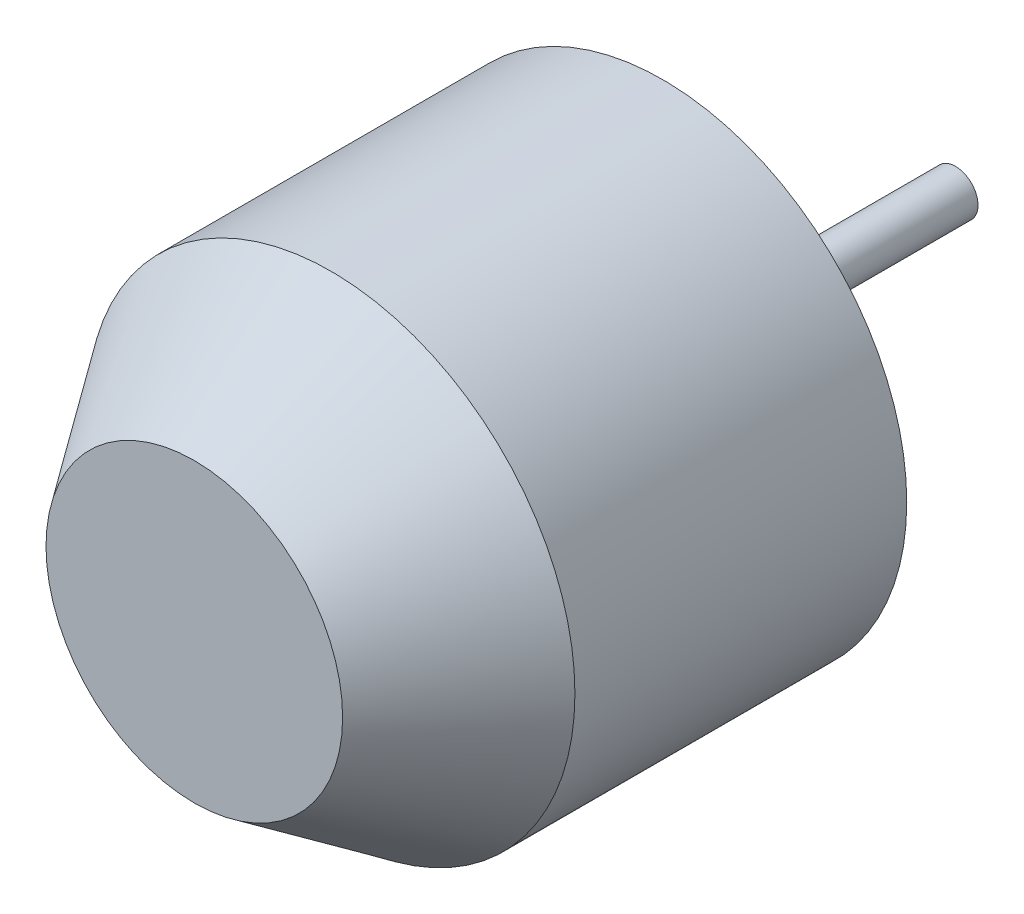
SolidWorks part; units mm, degrees
ref_plane "Plan de face" through (0, 0, 0) normal (0, 0, 1) x (1, 0, 0)
ref_plane "Plan de dessus" through (0, 0, 0) normal (0, 1, 0) x (1, 0, 0)
ref_plane "Plan de droite" through (0, 0, 0) normal (1, 0, 0) x (0, 0, -1)
sketch "Esquisse1" plane through (0, 0, 0) normal (0, 0, 1) x (1, 0, 0)
  circle A0 centre (0, 0) radius 12.5
  dimension "D1" = 25
extrude "Boss.-Extru.1" add sketch "Esquisse1" along normal blind 17 contours A0
sketch "Esquisse2" plane through (0, 0, 17) normal (0, 0, 1) x (1, 0, 0)
  circle A0 centre (0, 0) radius 12.5 construction
  circle A1 centre (0, 0) radius 12.5
extrude "Boss.-Extru.2" add sketch "Esquisse2" along normal blind 7 draft 35
sketch "Esquisse3" plane through (0, 0, 0) normal (0, 0, -1) x (-1, 0, 0)
  line L0 (-12.5, 0) -> (12.5, 0) construction
  circle A0 centre (0, 0) radius 12.5 construction
  circle A1 centre (-8, 0) radius 1.5
  circle A2 centre (8, 0) radius 1.5
  dimension "D3" = 3
  dimension "D4" = 3
  dimension "D1" = 8
  dimension "D2" = 8
extrude "Enlèv. mat.-Extru.1" cut sketch "Esquisse3" against normal blind 10
fillet "Congé1" radius 0.5 2 edges at (-9.5, 0, 0) (6.5, 0, 0)
sketch "Esquisse4" plane through (0, 0, 0) normal (0, 0, -1) x (-1, 0, 0)
  circle A0 centre (0, 0) radius 3.5
  dimension "D1" = 7
extrude "Boss.-Extru.3" add sketch "Esquisse4" along normal blind 2
sketch "Esquisse5" plane through (0, 0, -2) normal (0, 0, -1) x (-1, 0, 0)
  circle A0 centre (0, 0) radius 1.15
  dimension "D1" = 2.3
extrude "Boss.-Extru.4" add sketch "Esquisse5" along normal blind 13
